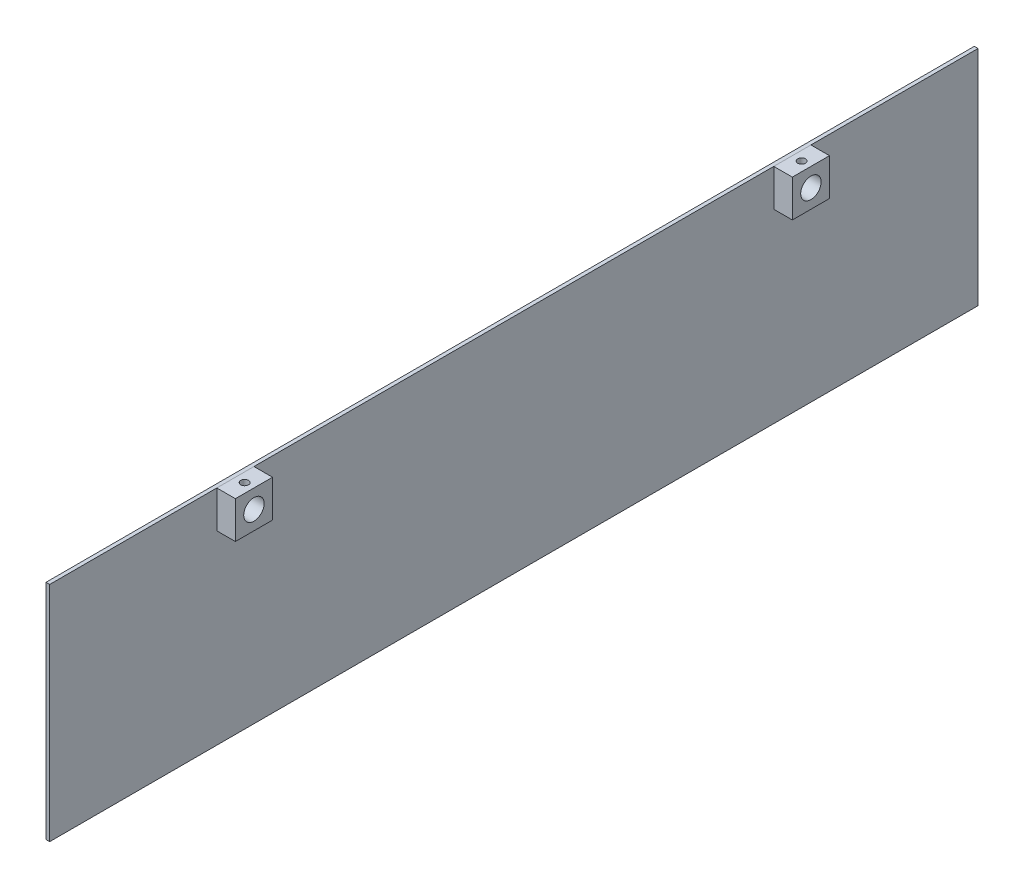
SolidWorks part; units mm, degrees
material "1.4301 (X5CrNi18-10)"
ref_plane "Vorne" through (0, 0, 0) normal (0, 0, 1) x (1, 0, 0)
ref_plane "Oben" through (0, 0, 0) normal (0, 1, 0) x (1, 0, 0)
ref_plane "Rechts" through (0, 0, 0) normal (1, 0, 0) x (0, 0, -1)
sketch "Skizze1" plane through (0, 0, 0) normal (0, 0, 1) x (1, 0, 0)
  line L0 (0, 0) -> (0, 120)
  dimension "D1" = 120
sheet metal parameters "Blech1" thickness 2 parameters "D1"=0.01, "Dicke"=2
base flange "Basis-Blech1" sketch "Skizze1" end condition mid plane depth 500 reverse direction yes thickness 2 reverse thickness direction no bend radius 0.01
sketch "Skizze6" plane through (2, 0, 0) normal (1, 0, 0) x (0, 0, -1)
  line L0 (250, 120) -> (-250, 120) construction
  line L1 (-160, 120) -> (-140, 120)
  line L2 (-160, 120) -> (-160, 100)
  line L3 (-160, 100) -> (-140, 100)
  line L4 (-140, 120) -> (-140, 100)
  line L5 (140, 120) -> (160, 120)
  line L6 (140, 120) -> (140, 100)
  line L7 (140, 100) -> (160, 100)
  line L8 (160, 120) -> (160, 100)
  point P8 (150, 100)
  point P9 (-150, 100)
  dimension "D1" = 20
  dimension "D2" = 150
  dimension "D3" = 150
extrude "Aufsatz-Linear austragen1" add sketch "Skizze6" along normal blind 10 separate body
hole_wizard "Ø11.0 (11) Durchmesser Bohrung1" positions "Skizze5" profile "Skizze4" hole size "Ø11.0" standard "Gabler-Normteile"
sketch "Skizze5" plane through (0, 4.2129, 147.0849) normal (1, 0, 0) x (0, 0, -1)
  line L0 (397.0849, 115.7871) -> (-102.9151, 115.7871) construction
  point P0 (-2.9151, 105.7871)
  point P2 (297.0849, 105.7871)
  dimension "D1" = 300
  dimension "D2" = 150
  dimension "D3" = 10
sketch "Skizze4" plane through (0, 110, 150) normal (0, 1, 0) x (0, 0, 1)
  line L0 (0, 0) -> (0, 23.3047)
  line L1 (0, 23.3047) -> (5.5, 20)
  line L2 (5.5, 20) -> (5.5, 0)
  line L5 (5.5, 0) -> (0, 0)
  line L10 (0, 23.3047) -> (-5.5, 20) construction
  line L11 (0, -6.35) -> (0, 107.95) construction
  dimension "Bohrerdurchmesser" = 11
  dimension "Bohrungstiefe" = 20
  dimension "Spitzenwinkel" = 118
hole_wizard "M5 Gewindebohrung1" positions "Skizze8" profile "Skizze7" tap size "M5" standard "Gabler-Normteile"
sketch "Skizze8" plane through (0, 120, 0) normal (0, 1, 0) x (1, 0, 0)
  line L0 (12, 160) -> (12, 140) construction
  line L1 (12, 140) -> (2, 140) construction
  line L2 (12, -160) -> (2, -160) construction
  line L3 (12, -140) -> (12, -160) construction
  point P0 (7, -150)
  point P2 (7, 150)
  dimension "D1" = 5
  dimension "D2" = 10
  dimension "D3" = 10
  dimension "D4" = 5
sketch "Skizze7" plane through (7, 120, 150) normal (1, 0, 0) x (0, 0, 1)
  line L0 (0, 0) -> (0, 15.2618)
  line L1 (0, 15.2618) -> (2.1, 14)
  line L2 (2.1, 14) -> (2.1, 0)
  line L5 (2.1, 0) -> (0, 0)
  line L10 (0, 15.2618) -> (-2.1, 14) construction
  line L11 (0, -6.35) -> (0, 107.95) construction
  dimension "Bohrerdurchmesser" = 4.2
  dimension "Bohrungstiefe" = 14
  dimension "Spitzenwinkel" = 118
cosmetic thread "Bohrungsgewinde1"
cosmetic thread "Bohrungsgewinde2"
flat pattern "Abwicklung1" [suppressed]
sketch "Biegung-Linien1" plane through (0, 0, 0) normal (0, 1, 0) x (1, 0, 0)
sketch3d "Rahmen1" [suppressed]
  line L0 (500, 0, 0) -> (0, 0, 0) construction
  line L1 (500, 120, 0) -> (0, 120, 0) construction
  line L2 (500, 0, 0) -> (500, 120, 0) construction
  line L3 (0, 0, 0) -> (0, 120, 0) construction
